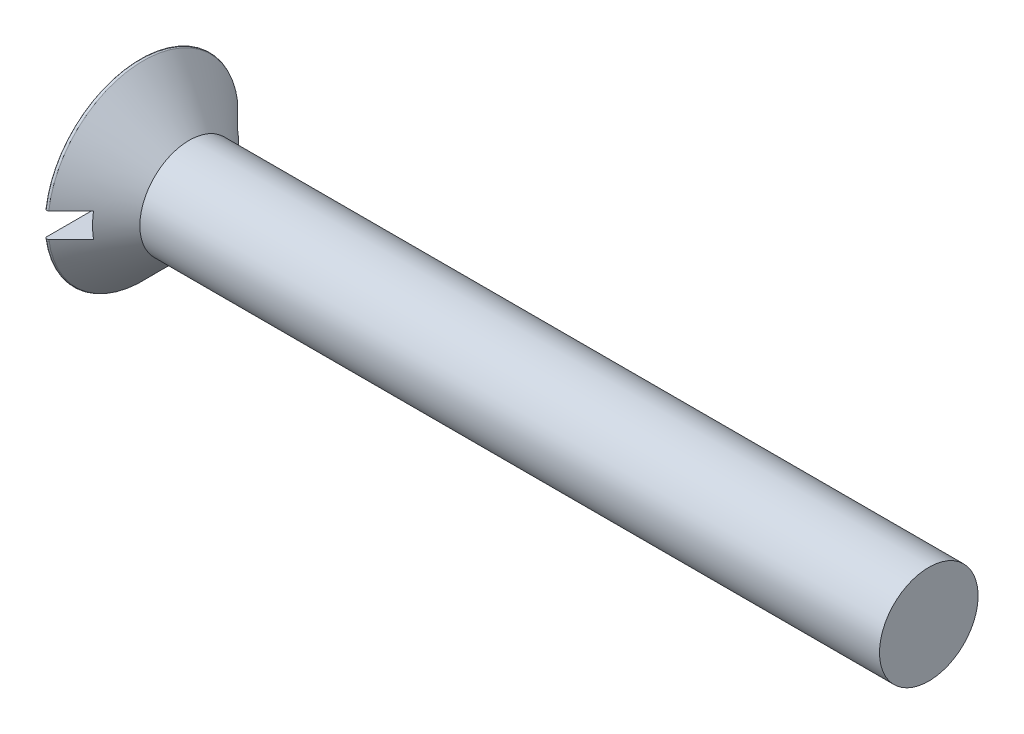
SolidWorks part; units mm, degrees
ref_plane "Front" through (0, 0, 0) normal (0, 0, 1) x (1, 0, 0)
ref_plane "Top" through (0, 0, 0) normal (0, 1, 0) x (1, 0, 0)
ref_plane "Right" through (0, 0, 0) normal (1, 0, 0) x (0, 0, -1)
sketch "Sketch1" plane through (0, 0, 0) normal (0, 0, 1) x (1, 0, 0)
  line L0 (0, 0) -> (0, 10)
  line L1 (0, 10) -> (5, 5)
  line L3 (80, 5) -> (80, 0)
  line L4 (80, 0) -> (0, 0)
  line L5 (-5.5696, 0) -> (0, 0) construction
  line L6 (5, 5) -> (80, 5)
  dimension "d" = 10
revolve "Base" add sketch "Sketch1" angle 360 about L5
cosmetic thread "ThreadCosmetic1" [suppressed] parameters "D1"=72, "D2"=8.376
fillet "HeadFillet" radius 0.2 1 edges at (0, 0, 10)
sketch "Sketch2" plane through (0, 0, 0) normal (0, 0, 1) x (1, 0, 0)
  line L1 (0, 1.25) -> (2.6, 1.25)
  line L2 (0, 1.25) -> (0, -1.25)
  line L3 (0, -1.25) -> (2.6, -1.25)
  line L4 (2.6, 1.25) -> (2.6, -1.25)
  dimension "m" = 1.25
extrude "Notch" cut sketch "Sketch2" against normal through all and the other way through all
sketch "Sketch3" plane through (0, 0, 0) normal (0, 0, 1) x (1, 0, 0)
  line L0 (4.4877, 0) -> (-0.464, 0) construction
  line L1 (5, 9.19) -> (41.5, 9.19)
  line L2 (5, 9.19) -> (5, 4.19)
  line L3 (5, 4.19) -> (37.7, 4.19)
  line L4 (41.5, 9.19) -> (41.5, 5)
  line L6 (41.5, 5) -> (37.7, 4.19)
  line L7 (80, -5) -> (80, 5) construction
  line L10 (0, 9.5172) -> (0, 1.25) construction
  dimension "b" = 38.5
  dimension "x" = 3.8
  dimension "D4" = 5
  dimension "d" = 10
sketch "Sketch4" plane through (0, 0, 0) normal (0, 0, 1) x (1, 0, 0)
  line L0 (80, 4.2968) -> (80.406, 5)
  line L1 (80.406, 5) -> (80.406, 5.812)
  line L2 (80.406, 5.812) -> (79.594, 5.812)
  line L3 (79.594, 5.812) -> (79.594, 5)
  line L4 (79.594, 5) -> (80, 4.2968)
  line L5 (80, -5) -> (80, 5) construction
  line L6 (0, 0) -> (84.1591, 0) construction
  dimension "D1" = 10
  dimension "D2" = 0.812
revolve "Cut-Revolve10" [suppressed] cut sketch "Sketch4" angle 360 about L6
pattern_linear "LPattern10" [suppressed] count 74 spacing 0.9744 along (-1, 0, 0) of bodies 104
equation "\"m@Sketch2\" = \"n@Sketch2\" / 2"
equation "\"D1@Sketch4\" = \"d@Sketch1\""
equation "\"D2@Sketch4\" =  ( \"d@Sketch1\" - \"D2@ThreadCosmetic1\" )  / 2"
equation "\"D3@LPattern10\" = \"D2@Sketch4\" * 1.2"
equation "\"D1@LPattern10\" = \"D1@ThreadCosmetic1\" / \"D3@LPattern10\""
